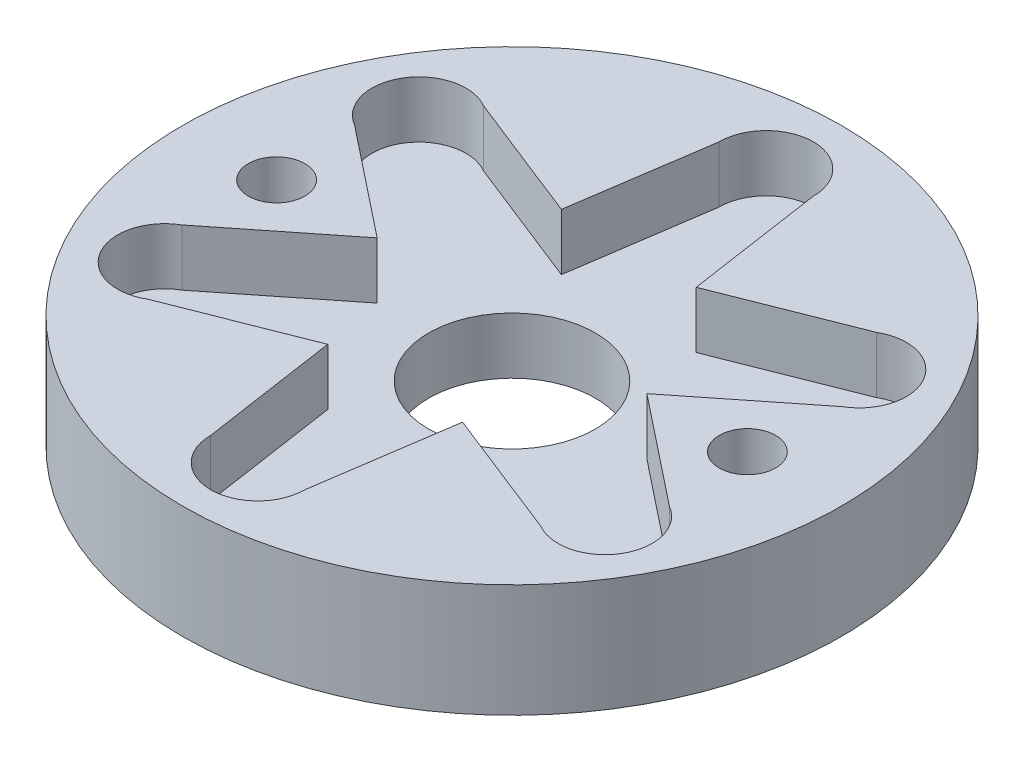
SolidWorks part; units mm, degrees
ref_plane "Front Plane" through (0, 0, 0) normal (0, 0, 1) x (1, 0, 0)
ref_plane "Top Plane" through (0, 0, 0) normal (0, 1, 0) x (1, 0, 0)
ref_plane "Right Plane" through (0, 0, 0) normal (1, 0, 0) x (0, 0, -1)
sketch "Sketch1" plane through (0, 0, 0) normal (0, 1, 0) x (1, 0, 0)
  line L0 (0, 0) -> (0, 16)
  line L2 (0, 13.5) -> (-2.5, 13.5)
  line L3 (0, 13.5) -> (2.5, 13.5)
  line L4 (-2.5, 13.5) -> (-4.5, 0)
  line L5 (2.5, 13.5) -> (4.5, 0)
  line L6 (0, 0) -> (13.8564, 8)
  line L8 (11.6913, 6.75) -> (10.4413, 8.9151)
  line L9 (11.6913, 6.75) -> (12.9413, 4.5849)
  line L10 (10.4413, 8.9151) -> (-2.25, 3.8971)
  line L11 (12.9413, 4.5849) -> (2.25, -3.8971)
  line L12 (0, 0) -> (13.8564, -8)
  line L14 (11.6913, -6.75) -> (12.9413, -4.5849)
  line L15 (11.6913, -6.75) -> (10.4413, -8.9151)
  line L16 (12.9413, -4.5849) -> (2.25, 3.8971)
  line L17 (10.4413, -8.9151) -> (-2.25, -3.8971)
  line L18 (0, 0) -> (0, -16)
  line L20 (0, -13.5) -> (2.5, -13.5)
  line L21 (0, -13.5) -> (-2.5, -13.5)
  line L22 (2.5, -13.5) -> (4.5, 0)
  line L23 (-2.5, -13.5) -> (-4.5, 0)
  line L24 (0, 0) -> (-13.8564, -8)
  line L26 (-11.6913, -6.75) -> (-10.4413, -8.9151)
  line L27 (-11.6913, -6.75) -> (-12.9413, -4.5849)
  line L28 (-10.4413, -8.9151) -> (2.25, -3.8971)
  line L29 (-12.9413, -4.5849) -> (-2.25, 3.8971)
  line L30 (0, 0) -> (-13.8564, 8)
  line L32 (-11.6913, 6.75) -> (-12.9413, 4.5849)
  line L33 (-11.6913, 6.75) -> (-10.4413, 8.9151)
  line L34 (-12.9413, 4.5849) -> (-2.25, -3.8971)
  line L35 (-10.4413, 8.9151) -> (2.25, 3.8971)
  circle A1 centre (0, 13.5) radius 2.5
  circle A3 centre (11.6913, 6.75) radius 2.5
  circle A5 centre (11.6913, -6.75) radius 2.5
  circle A7 centre (0, -13.5) radius 2.5
  circle A9 centre (-11.6913, -6.75) radius 2.5
  circle A10 centre (0, 0) radius 4.425
  circle A11 centre (-11.6913, 6.75) radius 2.5
  circle A12 centre (0, 0) radius 17.5
  point P53 (0, 0)
  dimension "D1" = 8.85
  dimension "D7" = 35
  dimension "D2" = 16
  dimension "D3" = 2.5
  dimension "D4" = 2.5
  dimension "D5" = 2.5
  dimension "D6" = 6
extrude "Boss-Extrude3" add sketch "Sketch1" along normal blind 6 contours A12 A11 L35 L4 A1 L5 L10 A3 L11 L16 A5 L17 L22 A7 L23 L28 A9 L29 L34 region at (-17.005, 0, 0)
extrude "Boss-Extrude5" add sketch "Sketch1<11>" along normal blind 3 contours L33 A11 L30 | L30 A11 L32 | L32 A11 L30 | L30 A11 L33 | A11 L30 L4 L35 | A11 L34 L29 L30 | L35 L4 L29 L10 | A10 L30 L4 L23 L24 | A10 L0 L10 L29 L30 | L29 L34 L23 L4 | A9 L24 L34 L29 | L24 A9 L27 | L27 A9 L24 | L24 A9 L26 | L26 A9 L24 | A9 L28 L23 L24 | A10 L24 L34 L17 L18 | L34 L23 L28 L17 | A7 L18 L28 L23 | A7 L22 L17 L18 | A10 L18 L28 L11 L12 | L28 L17 L22 L11 | L18 A7 L21 | L20 A7 L18 | L21 A7 L18 | L18 A7 L20 | A5 L12 L22 L17 | L15 A5 L12 | L14 A5 L12 | L12 A5 L15 | L12 A5 L14 | A5 L16 L11 L12 | A10 L12 L22 L5 L6 | L22 L11 L16 L5 | A3 L6 L16 L11 | A10 L6 L16 L35 L0 | L10 L35 L16 L5 | A3 L10 L5 L6 | L8 A3 L6 | L6 A3 L9 | L9 A3 L6 | L6 A3 L8 | A1 L0 L10 L5 | A1 L4 L35 L0 | L0 A1 L2 | L2 A1 L0 | L0 A1 L3 | L3 A1 L0 | A5 region at (-1.061, 0, -14.561) region at (1.061, 0, -12.439) region at (-1.061, 0, -12.439) region at (1.061, 0, -14.561) region at (1.6102, 0, -8.4409) region at (-1.6102, 0, -8.4409) region at (1.1071, 0, -4.2965) region at (-0.0488, 0, -4.6059) region at (-2.6346, 0, -4.5633) region at (2.6346, 0, -4.5633) region at (-6.5049, 0, -5.6149) region at (6.5049, 0, -5.6149) region at (-4.013, 0, -2.2611) region at (-5.2692, 0, 0) region at (-8.1151, 0, -2.826) region at (-10.2419, 0, -7.1384) region at (-12.0797, 0, -8.1994) region at (5.2692, 0, 0) region at (4.2749, 0, -1.1896) region at (8.1151, 0, -2.826) region at (12.0797, 0, -8.1994) region at (10.2419, 0, -7.1384) region at (-8.1151, 0, 2.826) region at (-11.303, 0, -5.3006) region at (-13.1407, 0, -6.3616) region at (11.303, 0, -5.3006) region at (8.1151, 0, 2.826) region at (13.1407, 0, -6.3616) region at (3.9644, 0, 2.3452) region at (-0.0488, 0, 4.6059) region at (-2.6346, 0, 4.5633) region at (-6.5049, 0, 5.6149) region at (-11.303, 0, 5.3006) region at (-13.1407, 0, 6.3616) region at (2.6346, 0, 4.5633) region at (6.5049, 0, 5.6149) region at (13.1407, 0, 6.3616) region at (11.303, 0, 5.3006) region at (1.6102, 0, 8.4409) region at (-1.6102, 0, 8.4409) region at (-10.2419, 0, 7.1384) region at (-12.0797, 0, 8.1994) region at (10.2419, 0, 7.1384) region at (12.0797, 0, 8.1994) region at (1.061, 0, 12.439) region at (-1.061, 0, 12.439) region at (-1.061, 0, 14.561) region at (1.061, 0, 14.561)
sketch "Sketch1<11>" plane through (0, 0, 0) normal (0, 1, 0) x (1, 0, 0) same geometry as "Sketch1"
sketch "Sketch2" plane through (0, 6, 0) normal (0, 1, 0) x (1, 0, 0)
  circle A0 centre (-12.5, 0) radius 1.5
  circle A1 centre (12.5, 0) radius 1.5
  dimension "D1" = 3
  dimension "D2" = 3
  dimension "D3" = 12.5
  dimension "D4" = 12.5
extrude "Cut-Extrude1" cut sketch "Sketch2" against normal blind 10
sketch "Sketch3" plane through (0, 0, 0) normal (0, -1, 0) x (1, 0, 0)
  circle A0 centre (-12.5, 0) radius 3
  circle A1 centre (12.5, 0) radius 3
  dimension "D1" = 6
  dimension "D2" = 6
extrude "Cut-Extrude2" cut sketch "Sketch3" against normal blind 1.5
